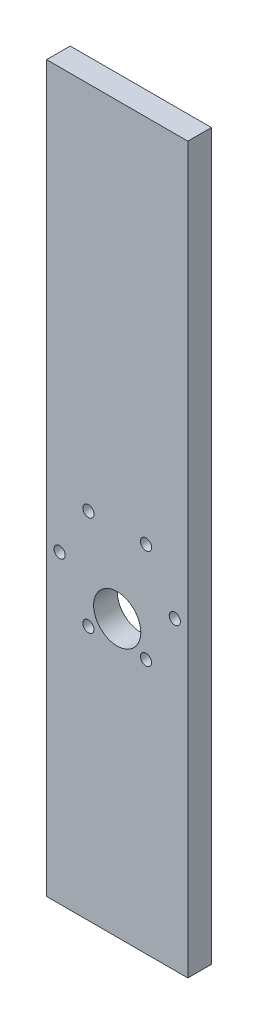
SolidWorks part; units mm, degrees
ref_plane "Alzado" through (0, 0, 0) normal (0, 0, 1) x (1, 0, 0)
ref_plane "Planta" through (0, 0, 0) normal (0, 1, 0) x (1, 0, 0)
ref_plane "Vista lateral" through (0, 0, 0) normal (1, 0, 0) x (0, 0, -1)
sketch "Croquis1" plane through (0, 0, 0) normal (0, 0, 1) x (1, 0, 0)
  line L1 (-19, -75) -> (19, -75)
  line L2 (-19, -75) -> (-19, 75)
  line L3 (-19, 75) -> (19, 75)
  line L4 (19, -75) -> (19, 75)
  line L5 (-19, -75) -> (19, 75) construction
  line L6 (-19, 75) -> (19, -75) construction
  point P0 (0, 0)
  dimension "D1" = 38
  dimension "D2" = 150
extrude "Saliente-Extruir1" add sketch "Croquis1" along normal mid plane 6.35
sketch "Croquis3" plane through (0, 0, 3.175) normal (0, 0, 1) x (1, 0, 0)
  line L0 (0, 99.9235) -> (0, -102.4325) construction
  line L1 (-92.4199, 0) -> (74.7437, 0) construction
  line L2 (-19, -75) -> (19, -75) construction
  line L3 (27.734, -23) -> (-27.5116, -23) construction
  circle A1 centre (-15.5, -23) radius 1.5
  circle A2 centre (0, -23) radius 15.5 construction
  circle A3 centre (-7.75, -9.5766) radius 1.5
  circle A4 centre (7.75, -9.5766) radius 1.5
  circle A5 centre (15.5, -23) radius 1.5
  circle A6 centre (7.75, -36.4234) radius 1.5
  circle A7 centre (-7.75, -36.4234) radius 1.5
  circle A8 centre (0, -30.8) radius 6.35
  point P27 (0, -23)
  dimension "D1" = 12.7
  dimension "D3" = 3
  dimension "D5" = 31
  dimension "D2" = 52
  dimension "D4" = 15.5
  dimension "D7" = 7.75
  dimension "D8" = 7.8
  dimension "D6" = 6
extrude "Cortar-Extruir2" cut sketch "Croquis3" against normal blind 25.4
sketch "Croquis8" plane through (0, 75, 0) normal (0, 1, 0) x (1, 0, 0)
  line L4 (19, 3.175) -> (-19, 3.175)
  line L5 (-19, 3.175) -> (-19, -3.175)
  line L6 (-19, -3.175) -> (19, -3.175)
  line L7 (19, -3.175) -> (19, 3.175)
  line L8 (19, 3.175) -> (-19, 3.175)
  line L9 (-19, 3.175) -> (-19, -3.175)
  line L10 (-19, -3.175) -> (19, -3.175)
  line L11 (19, -3.175) -> (19, 3.175)
  dimension "D1" = 0
extrude "Saliente-Extruir2" add sketch "Croquis8" along normal blind 15
sketch "Croquis9" plane through (0, -75, 0) normal (0, -1, 0) x (1, 0, 0)
  line L4 (-19, -3.175) -> (19, -3.175)
  line L5 (19, -3.175) -> (19, 3.175)
  line L6 (19, 3.175) -> (-19, 3.175)
  line L7 (-19, 3.175) -> (-19, -3.175)
  line L8 (-19, -3.175) -> (19, -3.175)
  line L9 (19, -3.175) -> (19, 3.175)
  line L10 (19, 3.175) -> (-19, 3.175)
  line L11 (-19, 3.175) -> (-19, -3.175)
  dimension "D1" = 0
extrude "Saliente-Extruir3" add sketch "Croquis9" along normal blind 30
